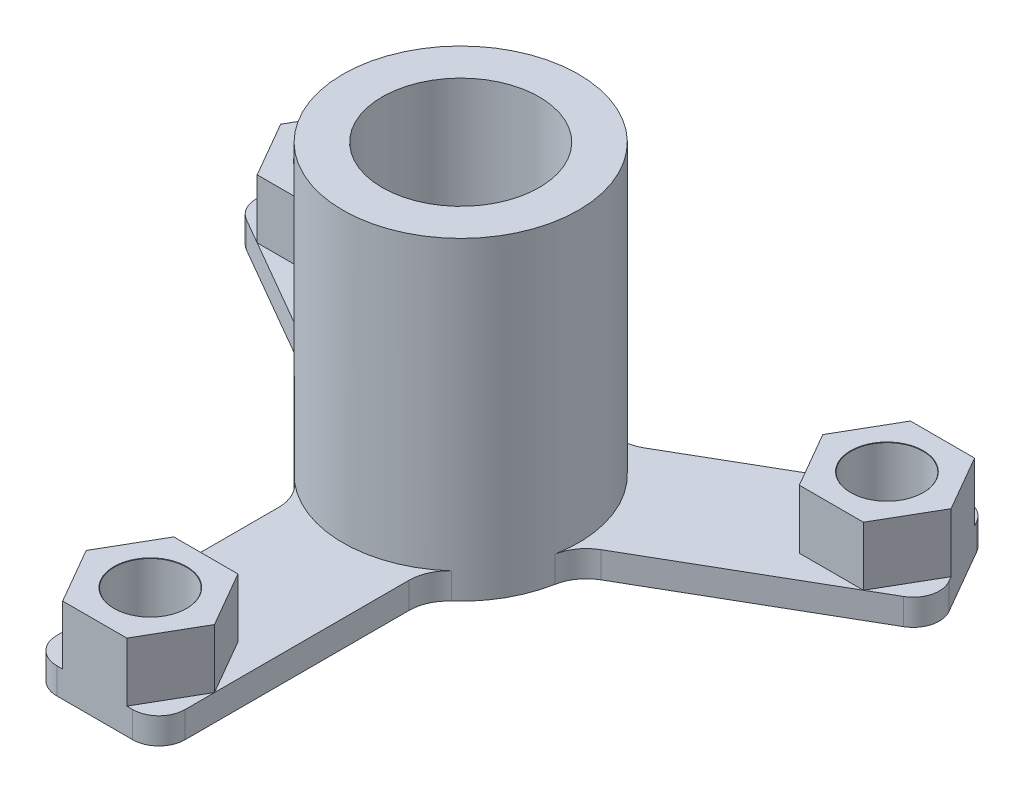
SolidWorks part; units mm, degrees
ref_plane "Plan de face" through (0, 0, 0) normal (0, 0, 1) x (1, 0, 0)
ref_plane "Plan de dessus" through (0, 0, 0) normal (0, 1, 0) x (1, 0, 0)
ref_plane "Plan de droite" through (0, 0, 0) normal (1, 0, 0) x (0, 0, -1)
sketch "Esquisse2" plane through (0, 0, 0) normal (0, 1, 0) x (1, 0, 0)
  circle A0 centre (0, 0) radius 9
  dimension "D1" = 18
extrude "Boss.-Extru.1" add sketch "Esquisse2" along normal blind 22
sketch "Esquisse5" plane through (0, 22, 0) normal (0, 1, 0) x (1, 0, 0)
  circle A0 centre (0, 0) radius 5
  dimension "D1" = 10
extrude "Boss.-Extru.3" add sketch "Esquisse5" against normal blind 2
sketch "Esquisse6" plane through (0, 22, 0) normal (0, 1, 0) x (1, 0, 0)
  circle A0 centre (0, 0) radius 6
  dimension "D1" = 12
extrude "Enlèv. mat.-Extru.2" cut sketch "Esquisse6" against normal blind 14
sketch "Esquisse7" plane through (0, 8, 0) normal (0, 1, 0) x (1, 0, 0)
  circle A0 centre (0, 0) radius 4
  dimension "D1" = 8
extrude "Enlèv. mat.-Extru.3" cut sketch "Esquisse7" against normal through all
sketch "Esquisse8" plane through (0, 0, 0) normal (0, -1, 0) x (1, 0, 0)
  circle A0 centre (0, 0) radius 5
  dimension "D1" = 10
extrude "Enlèv. mat.-Extru.4" cut sketch "Esquisse8" against normal blind 0.7
sketch "Esquisse9" plane through (0, 8, 0) normal (0, 1, 0) x (1, 0, 0)
  circle A0 centre (0, 0) radius 5
  dimension "D1" = 10
extrude "Enlèv. mat.-Extru.5" cut sketch "Esquisse9" against normal blind 0.7
sketch "Esquisse11" plane through (0, 0, 0) normal (0, -1, 0) x (1, 0, 0)
  circle A0 centre (0, 0) radius 5
  circle A1 centre (0, 0) radius 9
  dimension "D1" = 10
extrude "Boss.-Extru.4" add sketch "Esquisse11" along normal blind 2
sketch "Esquisse12" plane through (0, -2, 0) normal (0, -1, 0) x (1, 0, 0)
  line L2 (-4.8, 2.0125) -> (-4.8, 28.05)
  line L3 (-4.8, 28.05) -> (5, 28.05)
  line L4 (5, 1.4458) -> (5, 28.05)
  arc A0 (5, 1.4458) -> (-4.8, 2.0125) centre (0, 0) ccw
  dimension "D1" = 9.8
  dimension "D3" = 4.8
extrude "Boss.-Extru.5" add sketch "Esquisse12" against normal blind 2
pattern_circular "Répétition circulaire1" count 3 over 360 about axis through (0, 0, 0) along (0, 1, 0) of "Boss.-Extru.5"
sketch "Esquisse13" plane through (0, -2, 0) normal (0, -1, 0) x (1, 0, 0)
  line L0 (5, 28.05) -> (-4.8, 28.05) construction
  line L1 (-2.35, 28.05) -> (-4.8, 23.8065)
  line L2 (-4.8, 23.8065) -> (-2.35, 19.563)
  line L3 (-2.35, 19.563) -> (2.55, 19.563)
  line L4 (2.55, 19.563) -> (5, 23.8065)
  line L5 (5, 23.8065) -> (2.55, 28.05)
  line L6 (2.55, 28.05) -> (-2.35, 28.05)
  line L7 (5, 7.4833) -> (5, 28.05) construction
  circle A0 centre (0.1, 23.8065) radius 4.2435 construction
  point P10 (0, 0)
  dimension "D1" = 4.9
  dimension "D2" = 4.9
  dimension "D3" = 0
extrude "Boss.-Extru.6" add sketch "Esquisse13" against normal blind 6.5
pattern_circular "Répétition circulaire2" count 3 every 120 about axis through (0, 0, 0) along (0, 1, 0) of "Boss.-Extru.6"
hole_wizard "Dégagement M51" positions "Esquisse16" profile "Esquisse17" hole size "M5" standard "ISO" end condition through all
sketch "Esquisse16" plane through (0, 4.5, 0) normal (0, 1, 0) x (1, 0, 0)
  point P0 (0.1, -23.8065)
  dimension "D1" = 4.9
  dimension "D2" = 4.9
sketch "Esquisse17" plane through (0.1, 4.5, 23.8065) normal (1, 0, 0) x (0, 0, 1)
  line L0 (0, 0) -> (0, 6.5)
  line L1 (0, 6.5) -> (2.75, 6.5)
  line L2 (2.75, 6.5) -> (2.75, 0.025)
  line L3 (2.75, 0.025) -> (2.775, 0)
  line L5 (2.775, 0) -> (0, 0)
  line L6 (-2.75, 0.025) -> (-2.775, 0) construction
  line L11 (0, -6.35) -> (0, 107.95) construction
  dimension "Diamètre du perçage jusqu'au prochain" = 5.5
  dimension "Profondeur du perçage jusqu'au prochain" = 6.5
  dimension "Diamètre du fraisage entrant" = 5.55
  dimension "Angle du fraisage entrant" = 90
pattern_circular "Répétition circulaire3" count 3 every 120 about axis through (0, 22, 0) along (0, -1, 0) of "Dégagement M51"
fillet "Congé1" radius 3 1 edges at (-4.8, -1, 7.6131)
fillet "Congé2" radius 3 5 edges at (-4.1932, -1, -7.9635) (3.9807, -1, -8.0718) (8.9932, -1, 0.3503) (5, -1, 7.4833) (-8.9807, -1, 0.5885)
fillet "Congé3" radius 2 6 edges at (-21.892, -1, -18.1819) (-26.792, -1, -9.6949) (-4.8, -1, 28.05) (5, -1, 28.05) (26.692, -1, -9.8681) (21.792, -1, -18.3551)
